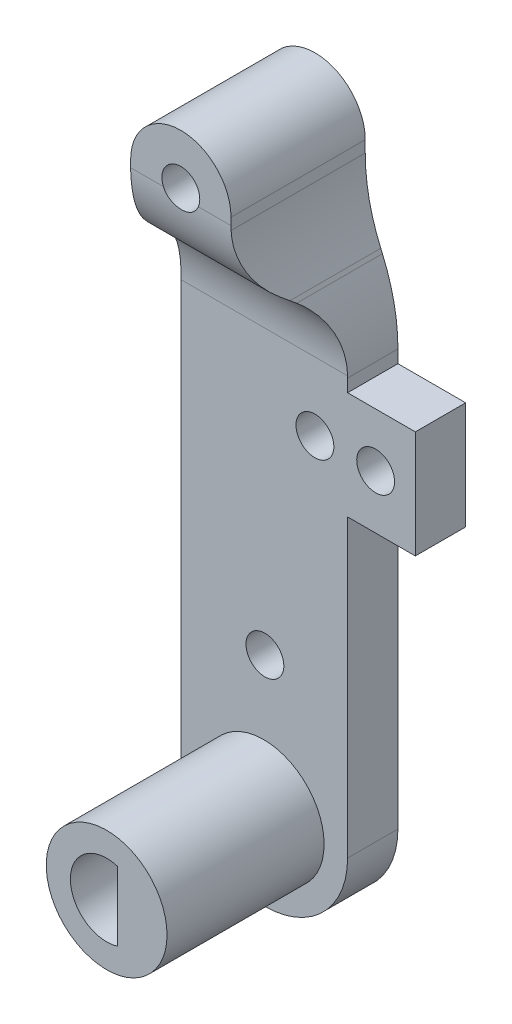
SolidWorks part; units mm, degrees
ref_plane "Front Plane" through (0, 0, 0) normal (0, 0, 1) x (1, 0, 0)
ref_plane "Top Plane" through (0, 0, 0) normal (0, 1, 0) x (1, 0, 0)
ref_plane "Right Plane" through (0, 0, 0) normal (1, 0, 0) x (0, 0, -1)
sketch "Sketch1" plane through (0, 0, 0) normal (0, 0, 1) x (1, 0, 0)
  line L0 (-5.898, 28.3342) -> (-5.898, 27.2476)
  line L1 (-2.8056, 11.5313) -> (-2.8056, 12.738)
  line L2 (3.6016, 11.5313) -> (3.6016, 1.3594)
  line L3 (-18.5662, 11.5313) -> (-18.5662, -26.5933)
  line L4 (3.6016, 1.3594) -> (-2.8056, 1.3594)
  line L5 (-2.8056, -26.5933) -> (-2.8056, 1.3594)
  line L6 (3.6016, 11.5313) -> (-2.8056, 11.5313)
  line L7 (-16.8793, 20.1661) -> (-17.0781, 19.7113)
  line L8 (-2.8056, 11.5313) -> (-18.5662, 11.5313) construction
  line L9 (-18.5662, 11.5313) -> (-18.5662, 12.5907)
  line L10 (-15.3912, 28.3342) -> (-15.3912, 27.2867)
  line L11 (-10.6859, -34.4736) -> (-36.5829, -34.4736) construction
  line L12 (-4.2728, 19.8107) -> (-4.4307, 20.1749)
  circle A0 centre (-10.6446, 28.3342) radius 1.7907
  circle A1 centre (-0.1512, 6.4513) radius 1.7907
  circle A2 centre (-5.898, 6.4513) radius 1.7907
  circle A3 centre (-10.6446, 28.3342) radius 4.7466
  circle A4 centre (-10.6859, -26.5933) radius 7.8803
  arc A5 (-18.5662, 12.5907) -> (-17.0781, 19.7113) centre (-0.7862, 12.5907) cw
  arc A6 (-15.3912, 27.2867) -> (-16.8793, 20.1661) centre (-33.1712, 27.2867) cw
  arc A7 (-5.898, 27.2476) -> (-4.4307, 20.1749) centre (11.882, 27.2476) ccw
  arc A8 (-2.8056, 12.738) -> (-4.2728, 19.8107) centre (-20.5856, 12.738) ccw
  circle A9 centre (-10.6287, -13.8687) radius 1.7907
  dimension "D1" = 17.78
  dimension "D2" = 3.5814
  dimension "D3" = 15.7606
  dimension "D4" = 3.5814
  dimension "D5" = 3.5814
  dimension "D6" = 7.9375
  dimension "D7" = 20.32
  dimension "D8" = 5.08
extrude "Boss-Extrude1" add sketch "Sketch1" along normal blind 12.7 contours A4 | L6 L8 L3 A4 L5 L4 L2 A2 A1 A9 | L8 L1 A8 L12 A7 L0 A3 L10 A6 L7 A5 L9 | A3 A0 region at (-10.6446, 23.7219, 0) region at (-9.8877, 1.7898, 0) region at (-10.6859, -26.5933, 0)
ref_plane "Plane2" through (0, -34.4736, 0) normal (0, -1, 0) x (-1, 0, 0)
sketch "Sketch5" plane through (-18.5662, 0, 0) normal (-1, 0, 0) x (0, 0, 1)
  line L0 (4.7625, -34.4736) -> (12.7, -34.4736)
  line L1 (12.7, -34.4736) -> (12.7, 27.6449)
  line L2 (-4.7625, -34.4736) -> (-12.7, -34.4736)
  line L3 (-12.7, -34.4736) -> (-12.7, 27.6449)
  line L4 (-4.7625, 11.2679) -> (-4.7625, 11.7056)
  line L5 (-12.7, 1.1079) -> (12.7, 1.1079)
  line L6 (-4.7625, -34.4736) -> (-4.7625, 11.2679)
  line L7 (4.7625, -34.4736) -> (4.7625, 11.2679)
  line L8 (4.7625, 11.2679) -> (4.7625, 12.9164)
  line L9 (-8.2114, 18.6734) -> (-9.3273, 19.5245)
  line L10 (8.2114, 19.8842) -> (9.2511, 20.6771)
  line L11 (12.7, -26.5933) -> (12.7, 12.5907) construction
  line L12 (-6.985, -34.4736) -> (6.985, -34.4736) construction
  line L14 (0, -26.5933) -> (0, 12.5907) construction
  arc A0 (4.7625, 12.9164) -> (8.2114, 19.8842) centre (13.5255, 12.9164) cw
  arc A1 (-4.7625, 11.7056) -> (-8.2114, 18.6734) centre (-13.5255, 11.7056) ccw
  arc A2 (12.7, 27.6449) -> (9.2511, 20.6771) centre (3.937, 27.6449) cw
  arc A3 (-12.7, 27.6449) -> (-9.3273, 19.5245) centre (-4.0131, 26.4923) ccw
  line M2 (0, -26.5933) -> (12.7, -26.5933)
  line M3 (12.7, -26.5933) -> (12.7, 12.5907)
  line M4 (12.7, 12.5907) -> (0, 12.5907)
  dimension "D1" = 8.763
  dimension "D3" = 4.7625
  dimension "D4" = 9.525
extrude "Cut-Extrude1" cut sketch "Sketch5" against normal through all contours L8 L7 L5 L1 M4 | L1 A2 L10 A0 L8 M4 | L7 L5 M2 M3 | L7 L0 L1 M2 region at (-18.5662, -30.5334, 8.7312) region at (-18.5662, -12.7427, 8.7312) region at (-18.5662, 6.8493, 8.7313) region at (-18.5662, 16.935, 9.5414)
sketch "Sketch6" plane through (0, 0, 4.7625) normal (0, 0, 1) x (1, 0, 0)
  line L0 (-9.7271, -23.2937) -> (-9.7271, -29.8437)
  line L1 (-2.8056, -26.5933) -> (-2.8056, 1.3594) construction
  circle A0 centre (-10.7431, -26.5687) radius 5.715
  circle A1 centre (-10.7431, -26.5687) radius 3.429
  circle A2 centre (-10.6287, -13.8687) radius 1.7907 construction
  dimension "D1" = 11.43
  dimension "D2" = 6.858
  dimension "D3" = 1.016
  dimension "D4" = 12.7
  dimension "D5" = 7.9375
extrude "Boss-Extrude2" add sketch "Sketch6" along normal blind 14.859 contours A0 A1 | L0 A1 region at (-8.7251, -26.5687, 4.7625) region at (-16.2964, -26.5687, 4.7625)
